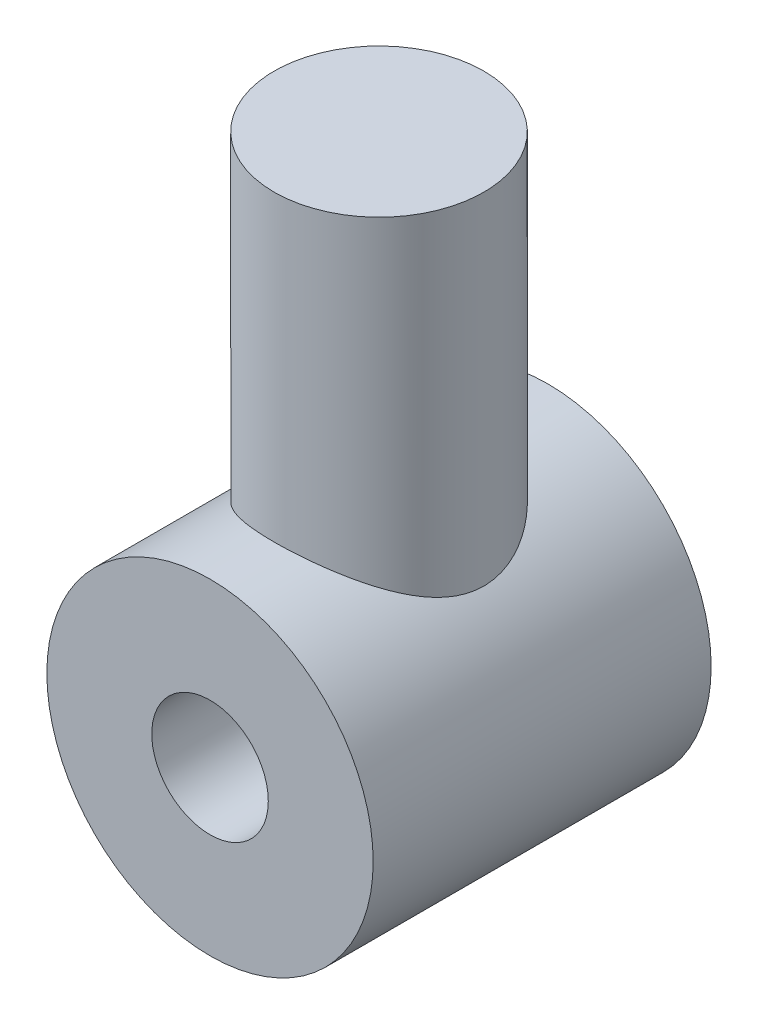
SolidWorks part; units mm, degrees
ref_plane "Front Plane" through (0, 0, 0) normal (0, 0, 1) x (1, 0, 0)
ref_plane "Top Plane" through (0, 0, 0) normal (0, 1, 0) x (1, 0, 0)
ref_plane "Right Plane" through (0, 0, 0) normal (1, 0, 0) x (0, 0, -1)
sketch "Sketch1" plane through (0, 0, 0) normal (0, 0, 1) x (1, 0, 0)
  circle A0 centre (0, 0) radius 14
  dimension "D1" = 28
extrude "Boss-Extrude1" add sketch "Sketch1" along normal blind 29
sketch "Sketch2" plane through (0, 0, 0) normal (0, 1, 0) x (1, 0, 0)
  line L0 (0, 0) -> (0, -29) construction
  line L1 (-14, -29) -> (14, -29) construction
  circle A0 centre (0, -14.5) radius 9
  dimension "D1" = 18
extrude "Boss-Extrude2" add sketch "Sketch2" along normal blind 40
sketch "Sketch3" plane through (0, 0, 29) normal (0, 0, 1) x (1, 0, 0)
  circle A0 centre (0, 0) radius 5
  dimension "D1" = 10
extrude "Cut-Extrude1" cut sketch "Sketch3" against normal through all
